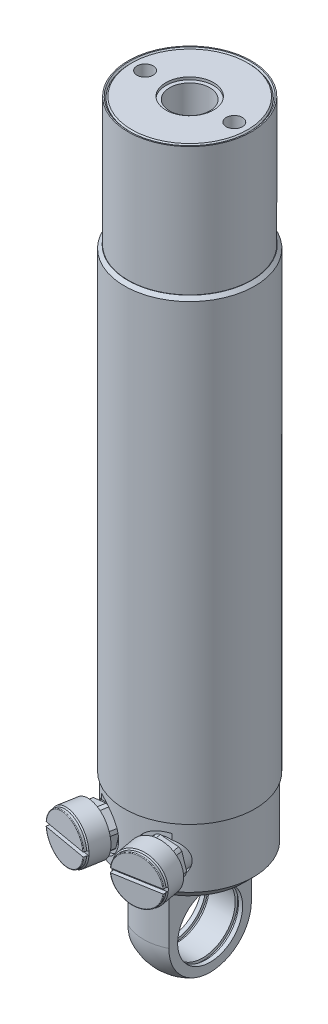
SolidWorks part; units mm, degrees
material "6061-T6 (SS)"
ref_plane "Front Plane" through (0, 0, 0) normal (0, 0, 1) x (1, 0, 0)
ref_plane "Top Plane" through (0, 0, 0) normal (0, 1, 0) x (1, 0, 0)
ref_plane "Right Plane" through (0, 0, 0) normal (1, 0, 0) x (0, 0, -1)
sketch "Sketch11" plane through (0, 0, 0) normal (0, 1, 0) x (1, 0, 0)
  circle A0 centre (0, 0) radius 24.13
  dimension "D1" = 48.26
extrude "Boss-Extrude6" add sketch "Sketch11" against normal blind 50.292
sketch "Sketch12" plane through (0, -50.292, 0) normal (0, -1, 0) x (1, 0, 0)
  circle A0 centre (0, 0) radius 25.527
  dimension "D1" = 51.054
extrude "Boss-Extrude7" add sketch "Sketch12" along normal blind 178.562
chamfer "Chamfer3" distance 1.27 angle 45 1 edges at (0, -50.292, -25.527)
sketch "Sketch23" plane through (0, 0, 0) normal (0, 1, 0) x (1, 0, 0)
  circle A0 centre (0, 0) radius 7.874
  dimension "D1" = 15.748
extrude "Cut-Extrude6" cut sketch "Sketch23" against normal blind 50.8
sketch "Sketch24" plane through (0, 0, 0) normal (0, 1, 0) x (1, 0, 0)
  circle A0 centre (0, 0) radius 9.3345
  dimension "D1" = 18.669
extrude "Cut-Extrude7" cut sketch "Sketch24" against normal blind 1.016
sketch "Sketch25" plane through (0, 0, 0) normal (0, 1, 0) x (1, 0, 0)
  circle A0 centre (0, 0) radius 22.6695
  dimension "D1" = 45.339
extrude "Cut-Extrude-Thin1" cut sketch "Sketch25" against normal blind 1.016 draft 45 thin thin type one direction wall 1.016
sketch "Sketch26" plane through (0, 0, 0) normal (0, 1, 0) x (1, 0, 0)
  line L0 (-17.4625, 0) -> (17.4625, 0) construction
  circle A0 centre (17.4625, 0) radius 3.175
  circle A1 centre (-17.4625, 0) radius 3.175
  dimension "D1" = 6.35
  dimension "D2" = 34.925
extrude "Cut-Extrude8" cut sketch "Sketch26" against normal blind 5.08
sketch "Sketch14" plane through (0, 0, 0) normal (0, 0, 1) x (1, 0, 0)
  line L0 (0, -129.9925) -> (0, -197.6721) construction
  line L1 (24.9301, -228.854) -> (24.9301, -252.2855)
  line L2 (-25.527, -228.854) -> (25.527, -228.854) construction
  line L3 (24.9301, -252.2855) -> (20.9296, -256.286)
  line L4 (20.9296, -256.286) -> (18.034, -256.286)
  line L5 (18.034, -256.286) -> (18.034, -276.86)
  line L6 (0, -294.894) -> (0, -228.854)
  line L7 (0, -228.854) -> (24.9301, -228.854)
  line L8 (24.13, 0) -> (-24.13, 0) construction
  arc A0 (18.034, -276.86) -> (0, -294.894) centre (0, -276.86) cw
  dimension "D1" = 36.068
  dimension "D2" = 49.8602
  dimension "D3" = 27.432
  dimension "D4" = 45
  dimension "D5" = 4.0005
  dimension "D6" = 276.86
revolve "Revolve2" add sketch "Sketch14" angle 360 about L0
fillet "Fillet1" radius 0.508 1 edges at (0, -256.286, 18.034)
sketch "Sketch15" plane through (0, 0, 0) normal (0, 0, 1) x (1, 0, 0)
  line L0 (-18.034, -256.286) -> (18.034, -256.286) construction
  line L1 (8.001, -256.286) -> (24.9301, -256.286)
  line L2 (8.001, -256.286) -> (8.001, -294.894)
  line L3 (8.001, -294.894) -> (24.9301, -294.894)
  line L4 (24.9301, -256.286) -> (24.9301, -294.894)
  line L5 (24.9301, -252.2855) -> (24.9301, -228.854) construction
  line L6 (0, -277.7335) -> (0, -302.146) construction
  arc A1 (-18.034, -276.86) -> (18.034, -276.86) centre (0, -276.86) ccw construction
  dimension "D1" = 16.002
extrude "Cut-Extrude3" cut sketch "Sketch15" against normal through all both and the other way through all
mirror "Mirror2" about plane through (0, 0, 0) normal (1, 0, 0) of "Cut-Extrude3"
fillet "Fillet2" radius 0.508 2 edges at (-8.001, -256.286, 0) (8.001, -256.286, 0)
sketch "Sketch27" plane through (0, 0, 0) normal (0, 0, 1) x (1, 0, 0)
  line L0 (-92.7615, -276.86) -> (-57.5568, -276.86) construction
  line L1 (-8.001, -276.86) -> (8.001, -276.86) construction
  line L2 (-8.001, -276.86) -> (8.001, -276.86)
  line L3 (8.001, -276.86) -> (8.001, -289.5981)
  line L4 (8.001, -293.022) -> (8.001, -276.86) construction
  line L5 (8.001, -289.5981) -> (6.35, -289.5981)
  line L6 (6.35, -289.5981) -> (6.35, -290.6141)
  line L7 (6.35, -290.6141) -> (5.08, -290.6141)
  line L8 (5.08, -290.6141) -> (5.08, -289.5981)
  line L9 (5.08, -289.5981) -> (-5.08, -289.5981)
  line L10 (-5.08, -289.5981) -> (-5.08, -290.6141)
  line L11 (-5.08, -290.6141) -> (-6.35, -290.6141)
  line L12 (-6.35, -290.6141) -> (-6.35, -289.5981)
  line L13 (-6.35, -289.5981) -> (-8.001, -289.5981)
  line L14 (-8.001, -276.86) -> (-8.001, -293.022) construction
  line L15 (-8.001, -289.5981) -> (-8.001, -276.86)
  dimension "D1" = 25.4762
  dimension "D2" = 1.016
  dimension "D3" = 1.27
  dimension "D4" = 10.16
revolve "Cut-Revolve1" cut sketch "Sketch27" angle 360 about L0
ref_point "Point1"
ref_plane "Plane1" through (0, 0, 0) normal (0.1736, 0, 0.9848) x (0, 1, 0)
sketch "Sketch28" plane through (0, 0, 0) normal (0.1736, 0, 0.9848) x (0, 1, 0)
  line L0 (-252.2855, 0) -> (-228.854, 0) construction
  line L1 (-228.854, 24.9301) -> (-228.854, -24.9301) construction
  circle A0 centre (-241.554, -7.874) radius 6.985
  dimension "D1" = 7.874
  dimension "D2" = 13.97
  dimension "D3" = 12.7
extrude "Cut-Extrude9" cut sketch "Sketch28" along normal through all
sketch "Sketch29" plane through (0, 0, 0) normal (0.1736, 0, 0.9848) x (0.9848, 0, -0.1736)
  circle A0 centre (7.874, -241.554) radius 9.144
  dimension "D1" = 18.288
extrude "Cut-Extrude10" cut sketch "Sketch29" along normal through all from offset 22.86
sketch "Sketch30" plane through (0, 0, 0) normal (0.1736, 0, 0.9848) x (0.9848, 0, -0.1736)
  circle A0 centre (7.874, -241.554) radius 6.35
  dimension "D1" = 12.7
extrude "Boss-Extrude8" add sketch "Sketch30" along normal blind 23.622 separate body
sketch "Sketch31" plane through (4.1019, 0, 23.2631) normal (0.1736, 0, 0.9848) x (0.9848, 0, -0.1736)
  line L1 (13.6408, -235.8003) -> (5.7746, -233.6829)
  line L2 (5.7746, -233.6829) -> (0.0078, -239.4366)
  line L3 (0.0078, -239.4366) -> (2.1072, -247.3077)
  line L4 (2.1072, -247.3077) -> (9.9734, -249.4251)
  line L5 (9.9734, -249.4251) -> (15.7402, -243.6714)
  line L6 (15.7402, -243.6714) -> (13.6408, -235.8003)
  circle A0 centre (7.874, -241.554) radius 7.747
  circle A1 centre (7.874, -241.554) radius 7.0549 construction
  circle M1 centre (7.874, -241.554) radius 6.35
  dimension "D1" = 15.494
  dimension "D2" = 14.1097
extrude "Boss-Extrude9" add sketch "Sketch31" along normal blind 4.1402 contours M1 | L6 A0 L1 L2 L3 L4 L5 M1 region at (17.1065, -236.235, 20.9701) region at (11.8563, -241.554, 21.8958)
sketch "Sketch32" plane through (4.8209, 0, 27.3404) normal (0.1736, 0, 0.9848) x (0.9848, 0, -0.1736)
  circle A0 centre (7.874, -241.554) radius 9.525
  dimension "D1" = 19.05
extrude "Boss-Extrude10" add sketch "Sketch32" along normal blind 7.4168 separate body
sketch "Sketch33" plane through (6.1088, 0, 34.6446) normal (0.1736, 0, 0.9848) x (0.9848, 0, -0.1736)
  circle A0 centre (7.874, -241.554) radius 9.0805
  dimension "D1" = 18.161
extrude "Boss-Extrude11" add sketch "Sketch33" along normal blind 1.6002
fillet "Fillet3" radius 0.254 1 edges at (23.0836, -241.554, 33.2763)
sketch "Sketch34" plane through (6.1088, 0, 34.6446) normal (0.1736, 0, 0.9848) x (0.9848, 0, -0.1736)
  line L1 (-1.2065, -242.3795) -> (16.9545, -242.3795)
  line L2 (-1.2065, -242.3795) -> (-1.2065, -240.7285)
  line L3 (-1.2065, -240.7285) -> (16.9545, -240.7285)
  line L4 (16.9545, -242.3795) -> (16.9545, -240.7285)
  line L5 (-1.2065, -242.3795) -> (16.9545, -240.7285) construction
  line L6 (-1.2065, -240.7285) -> (16.9545, -242.3795) construction
  circle A0 centre (7.874, -241.554) radius 9.0805 construction
  point P0 (7.874, -241.554)
  dimension "D1" = 1.651
extrude "Cut-Extrude11" cut sketch "Sketch34" along normal through all
chamfer "Chamfer4" distance 0.4572 angle 45 2 edges at (13.8631, -250.6345, 33.2772) (13.8631, -232.4735, 33.2772)
mirror "Mirror3" about plane through (0, 0, 0) normal (1, 0, 0) of "Cut-Extrude10", "Cut-Extrude9"
mirror "Mirror4" about plane through (0, 0, 0) normal (1, 0, 0) of bodies 130 133
